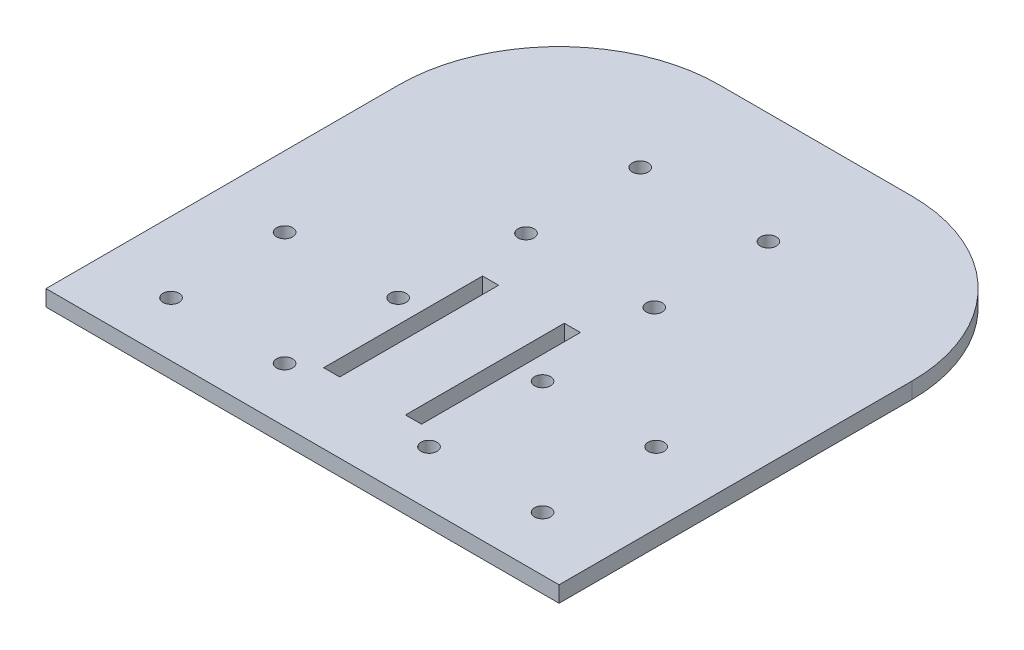
SolidWorks part; units mm, degrees
material "Acrylic (Medium-high impact)"
ref_plane "Front Plane" through (0, 0, 0) normal (0, 0, 1) x (1, 0, 0)
ref_plane "Top Plane" through (0, 0, 0) normal (0, 1, 0) x (1, 0, 0)
ref_plane "Right Plane" through (0, 0, 0) normal (1, 0, 0) x (0, 0, -1)
sketch "Sketch1" plane through (0, 0, 0) normal (0, 1, 0) x (1, 0, 0)
  line L1 (-101.6, -101.6) -> (101.6, -101.6)
  line L2 (-101.6, -101.6) -> (-101.6, 101.6)
  line L3 (-101.6, 101.6) -> (101.6, 101.6)
  line L4 (101.6, -101.6) -> (101.6, 101.6)
  line L5 (-101.6, -101.6) -> (101.6, 101.6) construction
  line L6 (-101.6, 101.6) -> (101.6, -101.6) construction
  point P0 (0, 0)
  dimension "D1" = 203.2
  dimension "D2" = 203.2
extrude "Boss-Extrude1" add sketch "Sketch1" along normal blind 6.35
sketch "Sketch2" plane through (0, 6.35, 0) normal (0, 1, 0) x (1, 0, 0)
  line L9 (101.6, 38.1) -> (101.6, 101.6)
  line L10 (101.6, 101.6) -> (38.1, 101.6)
  line L11 (-38.1, 101.6) -> (-101.6, 101.6)
  line L12 (-101.6, 101.6) -> (-101.6, 38.1)
  arc A2 (101.6, 38.1) -> (38.1, 101.6) centre (38.1, 38.1) ccw
  arc A3 (-101.6, 38.1) -> (-38.1, 101.6) centre (-38.1, 38.1) cw
extrude "Cut-Extrude1" cut sketch "Sketch2" against normal through all
sketch "Sketch9" plane through (0, 0, 0) normal (0, -1, 0) x (1, 0, 0)
  line L0 (-38.766, 10.8317) -> (-38.512, 10.8317) construction
  line L1 (-38.766, 73.756) -> (-38.512, 73.756) construction
  line L2 (38.5855, 10.8317) -> (38.3315, 10.8317) construction
  line L3 (-38.512, 10.8317) -> (-32.162, 10.8317)
  line L4 (-38.512, 10.8317) -> (-38.512, 73.756)
  line L5 (-38.512, 73.756) -> (-32.162, 73.756)
  line L6 (-32.162, 10.8317) -> (-32.162, 73.756)
  line L7 (38.5855, 73.756) -> (38.3315, 73.756) construction
  line L8 (-101.6, 101.6) -> (101.6, 101.6) construction
  line L13 (38.3315, 73.756) -> (31.9815, 73.756)
  line L14 (38.3315, 73.756) -> (38.3315, 10.8317)
  line L15 (38.3315, 10.8317) -> (31.9815, 10.8317)
  line L16 (31.9815, 73.756) -> (31.9815, 10.8317)
  line L17 (-101.6, -38.1) -> (-101.6, 101.6) construction
  circle A0 centre (-47.7463, 64.7757) radius 3.175 construction
  circle A1 centre (-47.7463, 19.812) radius 3.175 construction
  circle A2 centre (-92.71, 19.812) radius 3.175 construction
  circle A3 centre (-92.71, 64.7757) radius 3.175 construction
  circle A4 centre (-25.4903, -11.842) radius 3.175 construction
  circle A5 centre (25.3097, -11.842) radius 3.175 construction
  circle A6 centre (25.3097, -57.054) radius 3.175 construction
  circle A7 centre (-25.4903, -57.054) radius 3.175 construction
  circle A8 centre (47.5658, 19.812) radius 3.175 construction
  circle A9 centre (92.5295, 19.812) radius 3.175 construction
  circle A10 centre (92.5295, 64.7757) radius 3.175 construction
  circle A11 centre (47.5658, 64.7757) radius 3.175 construction
  circle A12 centre (-25.4903, -31.4508) radius 3.175
  circle A13 centre (25.3097, -31.4508) radius 3.175
  circle A14 centre (-25.4903, -76.6628) radius 3.175
  circle A15 centre (25.3097, -76.6628) radius 3.175
  circle A16 centre (-47.7463, 80.0157) radius 3.175
  circle A17 centre (-92.71, 80.0157) radius 3.175
  circle A18 centre (-47.7463, 35.052) radius 3.16
  circle A19 centre (-92.71, 35.052) radius 3.2058
  circle A20 centre (47.5658, 80.0157) radius 3.175
  circle A21 centre (92.5295, 80.0157) radius 3.175
  circle A22 centre (47.5658, 35.052) radius 3.175
  circle A23 centre (92.5295, 35.052) radius 3.175
  dimension "D22" = 6.35
  dimension "D23" = 6.35
  dimension "D24" = 6.35
  dimension "D26" = 6.35
  dimension "D27" = 6.35
  dimension "D28" = 6.35
  dimension "D29" = 6.35
  dimension "D30" = 6.35
  dimension "D31" = 6.35
  dimension "D32" = 6.35
  dimension "D33" = 6.35
  dimension "D36" = 19.6088
  dimension "D37" = 19.6088
  dimension "D38" = 19.6088
  dimension "D40" = 15.24
  dimension "D41" = 15.24
  dimension "D44" = 6.35
  dimension "D45" = 6.35
  dimension "D46" = 6.35
  dimension "D47" = 6.35
  dimension "D48" = 6.35
  dimension "D49" = 6.35
  dimension "D50" = 6.4115
  dimension "D51" = 6.32
  dimension "D1" = 0.254
  dimension "D2" = 6.35
  dimension "D4" = 44.9637
  dimension "D5" = 63.5883
  dimension "D6" = 44.9637
  dimension "D7" = 54.6863
  dimension "D8" = 53.944
  dimension "D9" = 60.548
  dimension "D10" = 135.86
  dimension "D11" = 141.9453
  dimension "D12" = 125.0145
  dimension "D13" = 131.2955
  dimension "D14" = 140.2758
  dimension "D15" = 185.2395
  dimension "D16" = 190.6185
  dimension "D17" = 122.191
  dimension "D18" = 74.2999
  dimension "D19" = 102.1121
  dimension "D20" = 140.8441
  dimension "D21" = 3.175
  dimension "D25" = 147.3059
  dimension "D34" = 8.89
  dimension "D35" = 81.788
  dimension "D39" = 19.6088
  dimension "D42" = 15.24
  dimension "D43" = 15.24
  dimension "D52" = 15.24
  dimension "D53" = 15.24
  dimension "D54" = 15.24
  dimension "D55" = 15.24
extrude "Cut-Extrude2" [suppressed] cut sketch "Sketch9" against normal through all
sketch "Sketch10" plane through (0, 0, 0) normal (0, -1, 0) x (1, 0, 0)
  line L0 (-19.462, 10.8317) -> (-13.112, 10.8317)
  line L1 (-13.112, 10.8317) -> (-13.112, 73.756)
  line L2 (-13.112, 73.756) -> (-19.462, 73.756)
  line L3 (-19.462, 73.756) -> (-19.462, 10.8317)
  line L4 (-38.512, 10.8317) -> (-32.162, 10.8317)
  line L5 (-32.162, 10.8317) -> (-32.162, 73.756)
  line L6 (-32.162, 73.756) -> (-38.512, 73.756)
  line L7 (-38.512, 73.756) -> (-38.512, 10.8317)
  line L8 (-38.512, 10.8317) -> (-32.162, 10.8317) construction
  line L9 (-32.162, 10.8317) -> (-32.162, 73.756) construction
  line L10 (-32.162, 73.756) -> (-38.512, 73.756) construction
  line L11 (-38.512, 73.756) -> (-38.512, 10.8317) construction
  line L12 (38.3315, 73.756) -> (31.9815, 73.756)
  line L13 (31.9815, 73.756) -> (31.9815, 10.8317)
  line L14 (31.9815, 10.8317) -> (38.3315, 10.8317)
  line L15 (38.3315, 10.8317) -> (38.3315, 73.756)
  line L16 (38.3315, 73.756) -> (31.9815, 73.756) construction
  line L17 (31.9815, 73.756) -> (31.9815, 10.8317) construction
  line L18 (31.9815, 10.8317) -> (38.3315, 10.8317) construction
  line L19 (38.3315, 10.8317) -> (38.3315, 73.756) construction
  line L20 (12.9315, 73.756) -> (19.2815, 73.756)
  line L21 (19.2815, 73.756) -> (19.2815, 10.8317)
  line L22 (19.2815, 10.8317) -> (12.9315, 10.8317)
  line L23 (12.9315, 10.8317) -> (12.9315, 73.756)
  circle A1 centre (25.3097, -31.4508) radius 3.175
  circle A2 centre (25.3097, -31.4508) radius 3.175 construction
  circle A3 centre (-25.4903, -31.4508) radius 3.175
  circle A4 centre (-25.4903, -31.4508) radius 3.175 construction
  circle A5 centre (25.3097, -76.6628) radius 3.175
  circle A6 centre (25.3097, -76.6628) radius 3.175 construction
  circle A7 centre (-25.4903, -76.6628) radius 3.175
  circle A8 centre (-25.4903, -76.6628) radius 3.175 construction
  circle A9 centre (-92.71, 80.0157) radius 3.175
  circle A10 centre (-92.71, 80.0157) radius 3.175 construction
  circle A11 centre (-47.7463, 80.0157) radius 3.175
  circle A12 centre (-47.7463, 80.0157) radius 3.175 construction
  circle A13 centre (92.5295, 35.052) radius 3.175
  circle A14 centre (92.5295, 35.052) radius 3.175 construction
  circle A15 centre (47.5658, 35.052) radius 3.175
  circle A16 centre (47.5658, 35.052) radius 3.175 construction
  circle A17 centre (92.5295, 80.0157) radius 3.175
  circle A18 centre (92.5295, 80.0157) radius 3.175 construction
  circle A19 centre (47.5658, 80.0157) radius 3.175
  circle A20 centre (47.5658, 80.0157) radius 3.175 construction
  circle A21 centre (-92.71, 35.052) radius 3.2058
  circle A22 centre (-92.71, 35.052) radius 3.2058 construction
  circle A23 centre (-47.7463, 35.052) radius 3.16
  circle A24 centre (-47.7463, 35.052) radius 3.16 construction
  circle A25 centre (-73.66, 80.0157) radius 3.175
  circle A26 centre (-28.6963, 80.0157) radius 3.175
  circle A27 centre (-73.66, 35.052) radius 3.175
  circle A28 centre (-28.6963, 35.052) radius 3.175
  circle A29 centre (28.5158, 80.0157) radius 3.175
  circle A30 centre (73.4795, 80.0157) radius 3.175
  circle A31 centre (73.4795, 35.052) radius 3.175
  circle A32 centre (28.5158, 35.052) radius 3.175
  circle A33 centre (25.3097, -12.4008) radius 3.175
  circle A34 centre (-25.4903, -12.4008) radius 3.175
  circle A35 centre (-25.4903, -57.6128) radius 3.175
  circle A36 centre (25.3097, -57.6128) radius 3.175
  dimension "D17" = 6.35
  dimension "D19" = 6.35
  dimension "D21" = 6.35
  dimension "D24" = 6.35
  dimension "D25" = 6.35
  dimension "D26" = 6.35
  dimension "D27" = 6.35
  dimension "D28" = 6.35
  dimension "D29" = 6.35
  dimension "D30" = 6.35
  dimension "D31" = 6.35
  dimension "D32" = 6.35
  dimension "D15" = 25.4
  dimension "D16" = 25.4
  dimension "D18" = 19.05
  dimension "D20" = 19.05
  dimension "D22" = 19.05
  dimension "D23" = 19.05
  dimension "D33" = 19.05
  dimension "D34" = 19.05
  dimension "D35" = 19.05
  dimension "D36" = 19.05
  dimension "D37" = 19.05
  dimension "D38" = 19.05
  dimension "D39" = 19.05
  dimension "D40" = 19.05
  dimension "D1" = 0
  dimension "D2" = 0
  dimension "D3" = 0
  dimension "D4" = 0
  dimension "D5" = 0
  dimension "D6" = 0
  dimension "D7" = 0
  dimension "D8" = 0
  dimension "D9" = 0
  dimension "D10" = 0
  dimension "D11" = 0
  dimension "D12" = 0
  dimension "D13" = 0
  dimension "D14" = 0
extrude "Cut-Extrude4" cut sketch "Sketch10" against normal through all
